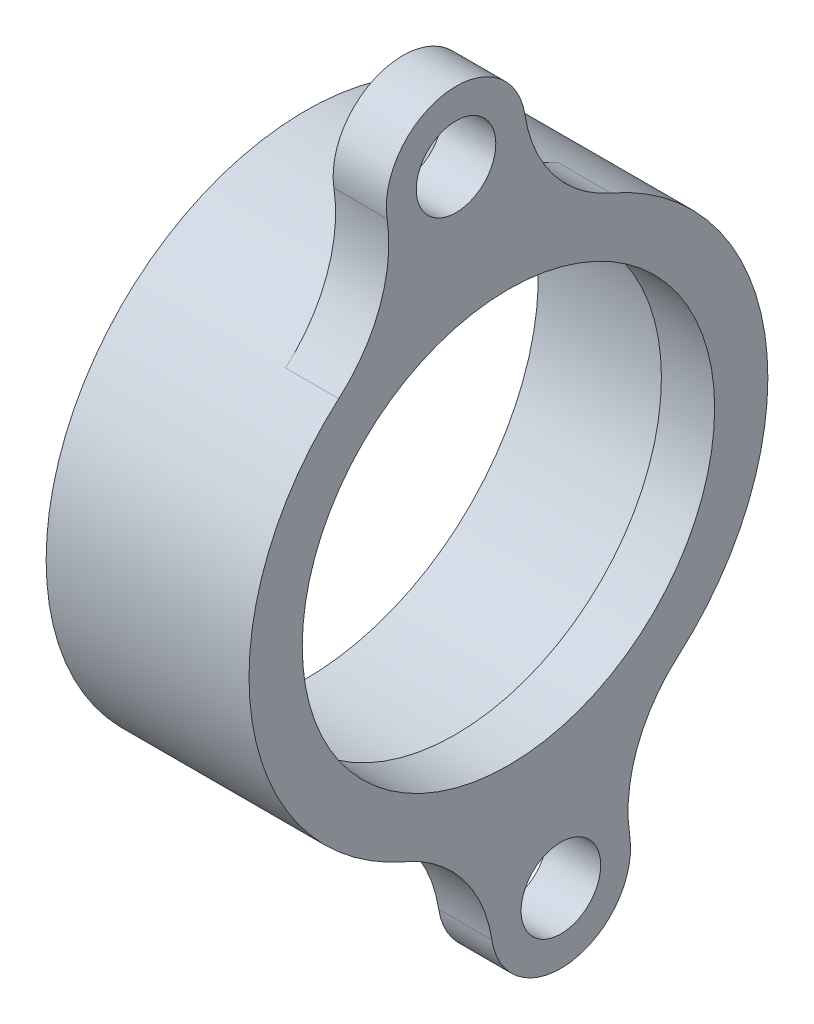
SolidWorks part; units mm, degrees
ref_plane "Front Plane" through (0, 0, 0) normal (0, 0, 1) x (1, 0, 0)
ref_plane "Top Plane" through (0, 0, 0) normal (0, 1, 0) x (1, 0, 0)
ref_plane "Right Plane" through (0, 0, 0) normal (1, 0, 0) x (0, 0, -1)
sketch "Sketch1" plane through (0, 0, 0) normal (0, 0, 1) x (1, 0, 0)
  line L0 (24.6062, 12.3825) -> (31.75, 12.3825)
  line L1 (31.75, 12.3825) -> (31.75, 11.1125)
  line L2 (31.75, 11.1125) -> (24.6062, 11.1125)
  line L4 (24.6062, 11.1125) -> (24.6062, 12.3825)
  line L5 (0, 0) -> (40.0174, 0) construction
  dimension "D1" = 1.27
  dimension "D2" = 7.1437
revolve "Revolve1" add sketch "Sketch1" angle 360 about L5
sketch "Sketch2" plane through (31.75, 0, 0) normal (1, 0, 0) x (0, 0, -1)
  line L0 (3.6897, -23.8296) -> (-3.6897, 23.8296) construction
  line L1 (-5.7902, 15.6496) -> (0.7862, 16.6678) construction
  line L2 (-11.4911, -1.7793) -> (11.4911, 1.7793) construction
  line L4 (-4.1591, 11.8861) -> (0.3697, 12.5873) construction
  line L5 (0.3697, 12.5873) -> (2.0268, 16.8599) construction
  line L6 (2.0268, 16.8599) -> (-0.8449, 20.4313) construction
  line L7 (-0.8449, 20.4313) -> (-5.3736, 19.7301) construction
  line L8 (-5.3736, 19.7301) -> (-7.0307, 15.4575) construction
  line L9 (-7.0307, 15.4575) -> (-4.1591, 11.8861) construction
  arc A0 (-8.0987, 9.3668) -> (-4.8868, -11.3774) centre (0, 0) ccw
  circle A1 centre (0, 0) radius 12.3825 construction
  arc A7 (0.7862, 16.6678) -> (-5.7902, 15.6496) centre (-2.502, 16.1587) ccw
  arc A8 (-8.0987, 9.3668) -> (-5.7902, 15.6496) centre (-12.617, 14.5925) ccw
  arc A9 (0.7862, 16.6678) -> (4.8868, 11.3774) centre (7.6131, 17.7249) ccw
  circle A10 centre (0, 0) radius 9.8425
  circle A11 centre (0, 0) radius 11.1125 construction
  arc A12 (5.7902, -15.6496) -> (8.0987, -9.3668) centre (12.617, -14.5925) cw
  arc A14 (5.7902, -15.6496) -> (-0.7862, -16.6678) centre (2.502, -16.1587) cw
  arc A15 (-4.8868, -11.3774) -> (-0.7862, -16.6678) centre (-7.6131, -17.7249) cw
  arc A16 (8.0987, -9.3668) -> (4.8868, 11.3774) centre (0, 0) ccw
  circle A17 centre (-2.502, 16.1587) radius 3.9688 construction
  arc A18 (1.5403, 20.0021) -> (-7.5172, 18.5996) centre (-2.9885, 19.3009) ccw construction
  arc A19 (-1.5403, -20.0021) -> (7.5172, -18.5996) centre (2.9885, -19.3009) ccw construction
  dimension "D1" = 1.27
  dimension "D2" = 3.3274
  dimension "D3" = 7.9375
extrude "Boss-Extrude1" add sketch "Sketch2" along normal blind 2.54
hole_wizard "#6 Clearance Hole1" positions "Sketch3" profile "Sketch5" hole size "#6" standard "ANSI Inch" end condition up to next
sketch "Sketch3" plane through (34.29, 0, 0) normal (1, 0, 0) x (0, 0, -1)
  point P0 (-2.502, 16.1587)
  point P3 (2.502, -16.1587)
sketch "Sketch5" plane through (34.29, 16.1587, 2.502) normal (0, 1, 0) x (0, 0, -1)
  line L0 (0, 0) -> (0, 2.54)
  line L1 (0, 2.54) -> (1.8986, 2.54)
  line L2 (1.8986, 2.54) -> (1.8986, 0)
  line L5 (1.8986, 0) -> (0, 0)
  line L11 (0, -6.35) -> (0, 107.95) construction
  dimension "Thru Hole Dia." = 3.7973
  dimension "Thru Hole Depth" = 2.54
